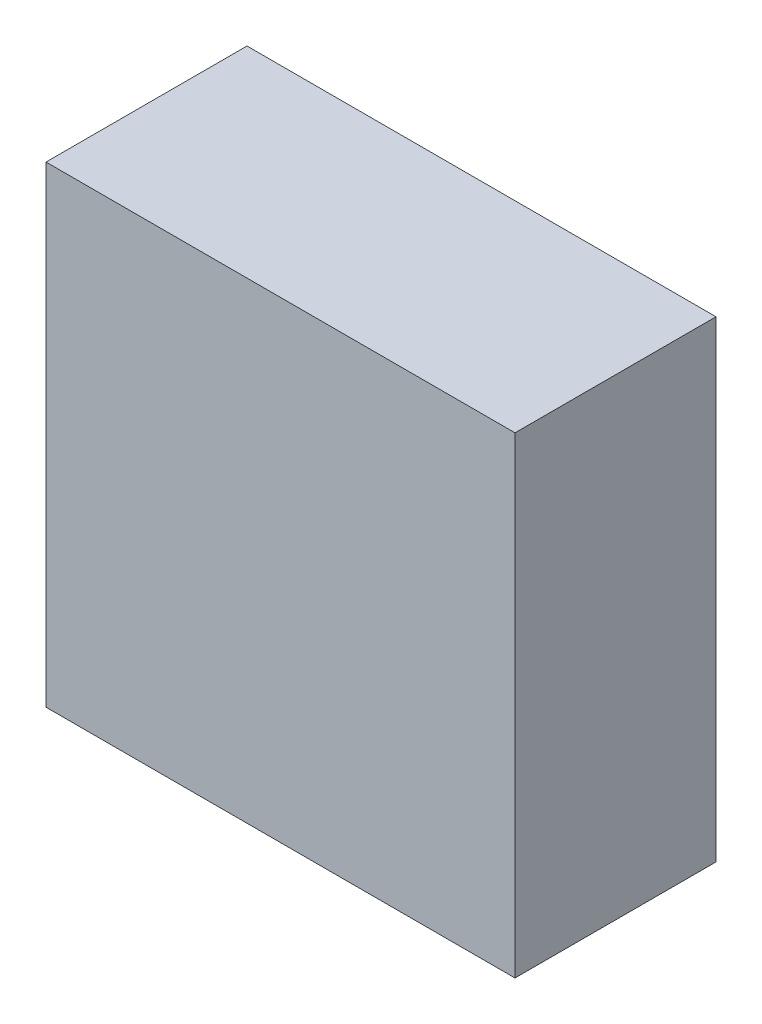
SolidWorks part; units mm, degrees
material "Pine"
ref_plane "Front Plane" through (0, 0, 0) normal (0, 0, 1) x (1, 0, 0)
ref_plane "Top Plane" through (0, 0, 0) normal (0, 1, 0) x (1, 0, 0)
ref_plane "Right Plane" through (0, 0, 0) normal (1, 0, 0) x (0, 0, -1)
sketch "Sketch1" plane through (0, 0, 0) normal (0, 1, 0) x (1, 0, 0)
  line L1 (-44.45, 19.05) -> (44.45, 19.05)
  line L2 (-44.45, 19.05) -> (-44.45, -19.05)
  line L4 (44.45, 19.05) -> (44.45, -19.05)
  line L5 (-44.45, 19.05) -> (44.45, -19.05) construction
  line L6 (-44.45, -19.05) -> (44.45, 19.05) construction
  line L7 (-44.45, -19.05) -> (44.45, -19.05)
  point P0 (0, 0)
  dimension "D1" = 88.9
  dimension "D2" = 38.1
extrude "Boss-Extrude1" add sketch "Sketch1" along normal blind 89.5
sketch "Sketch2" plane through (-44.45, 0, 0) normal (-1, 0, 0) x (0, 0, 1)
  line L0 (-19.05, 0) -> (19.05, 6.7181)
  line L1 (19.05, 89.5) -> (19.05, 0) construction
  line L2 (19.05, 6.7181) -> (19.05, 0)
  line L3 (19.05, 0) -> (-19.05, 0)
  dimension "D1" = 10
